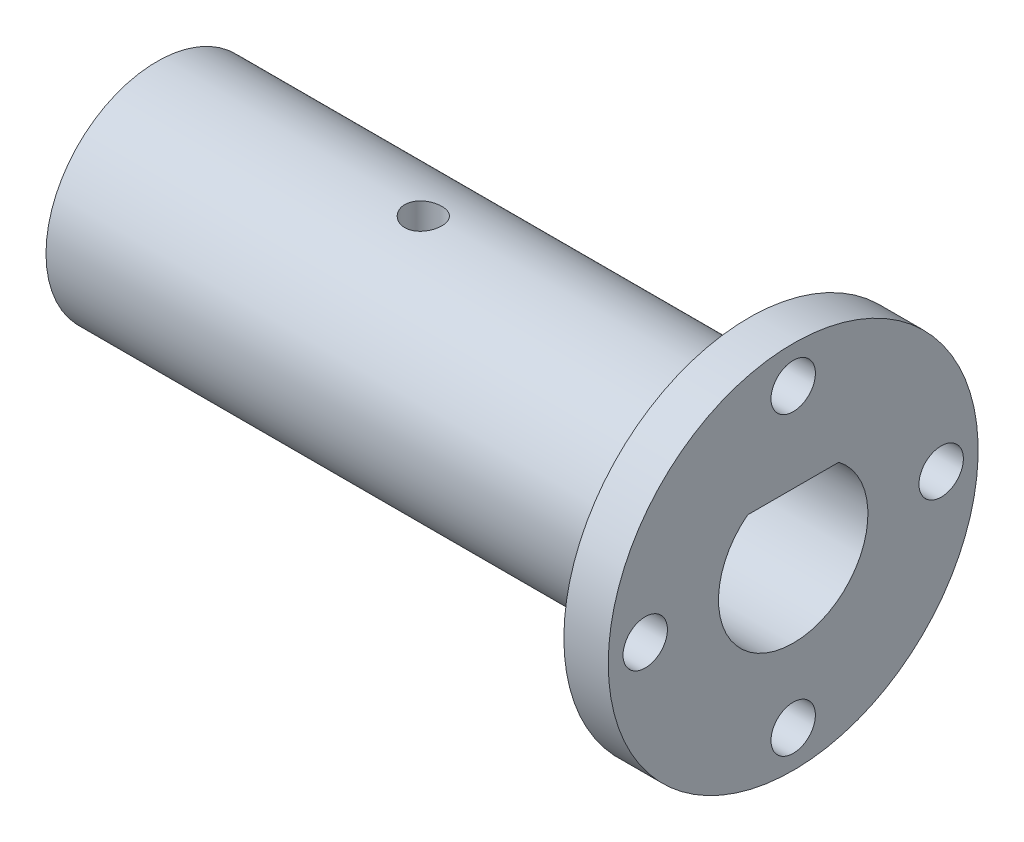
SolidWorks part; units mm, degrees
ref_plane "前视基准面" through (0, 0, 0) normal (0, 0, 1) x (1, 0, 0)
ref_plane "上视基准面" through (0, 0, 0) normal (0, 1, 0) x (1, 0, 0)
ref_plane "右视基准面" through (0, 0, 0) normal (1, 0, 0) x (0, 0, -1)
ref_plane "基准面1" through (0, 0, 0) normal (0, 0, -1) x (-1, 0, 0)
sketch "草图1" plane through (0, 0, 0) normal (0, 0, -1) x (-1, 0, 0)
  line L0 (-43, 12.5) -> (-43, 0)
  line L1 (-43, 0) -> (-40, 0)
  line L2 (-40, 0) -> (-40, 12.5)
  line L3 (-40, 12.5) -> (-43, 12.5)
  line L4 (-43, 0) -> (-40, 0) construction
revolve "旋转1" add sketch "草图1" angle 360 about L4 reverse direction yes
sketch "草图2" plane through (40, 0, 0) normal (-1, 0, 0) x (0, 0, 1)
  circle A0 centre (0, 0) radius 7.5
extrude "凸台-拉伸1" add sketch "草图2" along normal blind 40
sketch "草图3" plane through (0, 0, 0) normal (-1, 0, 0) x (0, 0, 1)
  line L0 (3.0826, 4) -> (-3.0826, 4)
  arc A0 (-3.0826, 4) -> (3.0826, 4) centre (0, 0) ccw
extrude "切除-拉伸1" cut sketch "草图3" against normal through all
hole_wizard "Ø3.0 (3) 直径孔3" positions "草图8" profile "草图7" hole size "Ø3.0" standard "ANSI Metric" end condition through all
sketch "草图8" plane through (40, 0, 0) normal (-1, 0, 0) x (0, 0, 1)
  point P0 (10, 0)
  point P1 (0, -10)
  point P2 (-10, 0)
  point P3 (0, 10)
sketch "草图7" plane through (40, 0, 10) normal (0, 1, 0) x (0, 0, 1)
  line L0 (0, 0) -> (0, 3)
  line L1 (0, 3) -> (1.5, 3)
  line L2 (1.5, 3) -> (1.5, 0)
  line L5 (1.5, 0) -> (0, 0)
  line L11 (0, -6.35) -> (0, 107.95) construction
  dimension "通孔孔直径" = 3
  dimension "通孔孔深度" = 3
sketch "草图9" plane through (0, 4, 0) normal (0, -1, 0) x (1, 0, 0)
  line L0 (0, 7.5) -> (0, -7.5) construction
  circle A0 centre (18, 0) radius 1.25
  dimension "D2" = 2.5
  dimension "D1" = 18
extrude "切除-拉伸2" cut sketch "草图9" against normal blind 10
